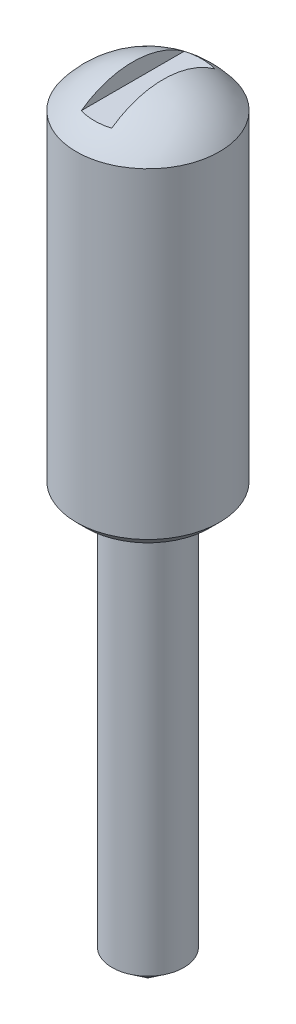
SolidWorks part; units mm, degrees
material "Латунь"
ref_plane "Спереди" through (0, 0, 0) normal (0, 0, 1) x (1, 0, 0)
ref_plane "Сверху" through (0, 0, 0) normal (0, 1, 0) x (1, 0, 0)
ref_plane "Справа" through (0, 0, 0) normal (1, 0, 0) x (0, 0, -1)
sketch "Эскиз2" plane through (0, 0, 0) normal (0, 0, 1) x (1, 0, 0)
  line L0 (0, 0) -> (2, 1.5)
  line L1 (2, 1.5) -> (2, 23.5)
  line L2 (2, 23.5) -> (4, 23.5)
  line L3 (4, 23.5) -> (4, 42)
  line L4 (4, 42) -> (0, 42)
  line L5 (0, 42) -> (0, 0)
  dimension "D1" = 2
  dimension "D2" = 1.5
  dimension "D3" = 4
  dimension "D4" = 22
  dimension "D5" = 42
revolve "Повернуть1" add sketch "Эскиз2" angle 360 about L5
cosmetic thread "Условное изображение резьбы1" parameters "D2"=6.891
dome "Купол1" faces to dome 1 distance 2 reverse direction no elliptical dome no face at (0, 42, 4) parameters "D1"=2
sketch "Эскиз3" plane through (0, 0, 0) normal (0, 0, 1) x (1, 0, 0)
  line L0 (-4, 42) -> (4, 42) construction
  line L1 (-0.85, 53) -> (0.85, 53)
  line L2 (-0.85, 53) -> (-0.85, 43)
  line L3 (-0.85, 43) -> (0.85, 43)
  line L4 (0.85, 53) -> (0.85, 43)
  line L5 (-0.85, 53) -> (0.85, 43) construction
  line L6 (-0.85, 43) -> (0.85, 53) construction
  point P0 (0, 48)
  dimension "D1" = 1.7
  dimension "D2" = 1
  dimension "D3" = 10
extrude "Вырез-Вытянуть1" cut sketch "Эскиз3" against normal through all and the other way through all
chamfer "Фаска1" distance 0.5545 angle 45 1 edges at (0, 23.5, 4)
